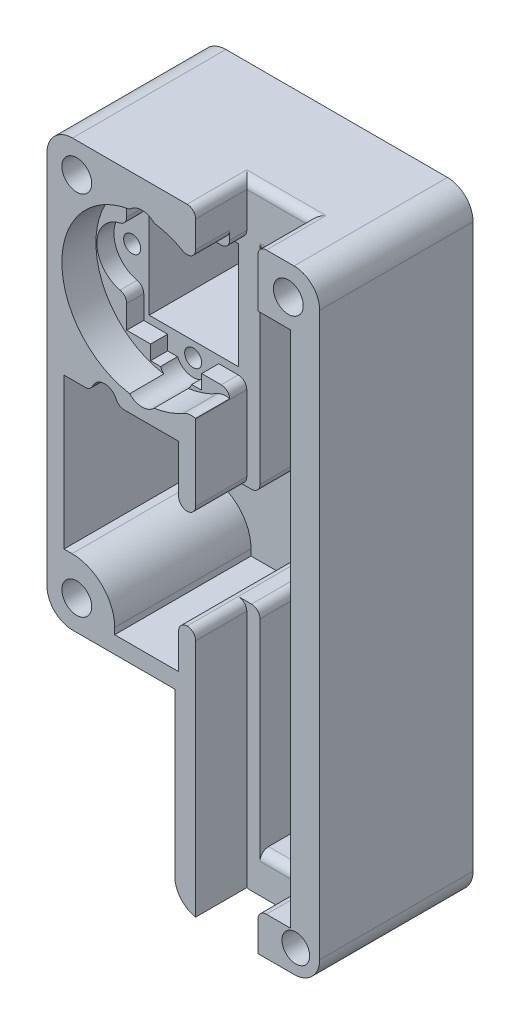
SolidWorks part; units mm, degrees
ref_plane "Ebene vorne" through (0, 0, 0) normal (0, 0, 1) x (1, 0, 0)
ref_plane "Ebene oben" through (0, 0, 0) normal (0, 1, 0) x (1, 0, 0)
ref_plane "Ebene rechts" through (0, 0, 0) normal (1, 0, 0) x (0, 0, -1)
sketch "body-sketch" plane through (0, 0, 0) normal (0, 0, 1) x (1, 0, 0)
  line L0 (-32, 50) -> (0, 50)
  line L1 (-32, 0) -> (-17, 0)
  line L2 (0, 50) -> (0, -22)
  line L3 (-17, -22) -> (-17, 0)
  line L4 (-32, 0) -> (-32, 50)
  line L5 (0, -22) -> (-17, -22)
  line L7 (-26, 43) -> (-15.5, 43)
  line L8 (-26, 43) -> (-26, 30.5)
  line L9 (-26, 30.5) -> (-15.5, 30.5)
  line L10 (-15.5, 43) -> (-15.5, 30.5)
  dimension "D1" = 32
  dimension "D2" = 50
  dimension "D3" = 17
  dimension "D4" = 72
  dimension "D5" = 12.5
  dimension "D6" = 10.5
  dimension "D7" = 7
  dimension "D8" = 6
extrude "body" add sketch "body-sketch" along normal mid plane 18
sketch "gear_box" plane through (0, 0, 9) normal (0, 0, 1) x (1, 0, 0)
  line L0 (-26, 43) -> (-15.5, 30.5) construction
  line L1 (-15.5, 30.5) -> (-15.5, 43) construction
  line L2 (-15.5, 43) -> (-26, 30.5) construction
  line L3 (0, 50) -> (-32, 50) construction
  line L4 (-32, 50) -> (-32, 0) construction
  circle A0 centre (-20.75, 36.75) radius 9.5
  dimension "D1" = 19
  dimension "D2" = 13.25
  dimension "D3" = 11.25
extrude "gear_profile" cut sketch "gear_box" against normal blind 4
sketch "screwhole1" plane through (0, 0, 9) normal (0, 0, 1) x (1, 0, 0)
  line L0 (0, 50) -> (-32, 50) construction
  line L1 (-32, 50) -> (-32, 0) construction
  line L2 (0, -22) -> (0, 50) construction
  line L3 (-17, -22) -> (0, -22) construction
  circle A0 centre (-28.5, 46.5) radius 1.75
  circle A1 centre (-3.6772, 46.5) radius 1.75
  circle A2 centre (-2.8, -19.2) radius 1.625
  dimension "D1" = 3.5
  dimension "D4" = 3.25
  dimension "D2" = 3.5
  dimension "D3" = 3.5
  dimension "D5" = 2.8
  dimension "D6" = 2.8
extrude "screw1" cut sketch "screwhole1" against normal through all
fillet "Verrundung2" radius 3 2 edges at (0, 50, 0) (-32, 50, 0)
sketch "glider" plane through (0, 0, 9) normal (0, 0, 1) x (1, 0, 0)
  line L0 (-17, 0) -> (-17, -22) construction
  line L1 (-13, 43.3) -> (-3.4, 43.3)
  line L2 (-13, 43.3) -> (-13, -17.5)
  line L3 (-13, -17.5) -> (-3.4, -17.5)
  line L4 (-3.4, 43.3) -> (-3.4, -17.5)
  line L6 (-15.5, 43) -> (-26, 43) construction
  dimension "D1" = 9.6
  dimension "D2" = 60.8
  dimension "D3" = 4
  dimension "D4" = 3.4
  dimension "D5" = 0.3
extrude "glider_rut" cut sketch "glider" against normal blind 16
fillet "Verrundung4" radius 2 1 edges at (-13, 31.2557, 7)
sketch "holder of glider" plane through (0, 0, -7) normal (0, 0, 1) x (1, 0, 0)
  line L0 (-8.2, 43.3) -> (-8.2, -17.5) construction
  line L2 (-3.4, 43.3) -> (-13, 43.3) construction
  line L3 (-13, -17.5) -> (-3.4, -17.5) construction
  line L5 (-11.2, 30.8) -> (-5.2, 30.8)
  line L6 (-11.2, 30.8) -> (-11.2, 22.8)
  line L7 (-11.2, 22.8) -> (-5.2, 22.8)
  line L8 (-5.2, 30.8) -> (-5.2, 22.8)
  line L9 (-11.2, 3) -> (-5.2, 3)
  line L10 (-11.2, 3) -> (-11.2, -5)
  line L11 (-11.2, -5) -> (-5.2, -5)
  line L12 (-5.2, 3) -> (-5.2, -5)
  line L13 (-11.2, 3) -> (-5.2, -5) construction
  line L14 (-11.2, -5) -> (-5.2, 3) construction
  line L15 (-11.2, 30.8) -> (-5.2, 22.8) construction
  line L16 (-11.2, 22.8) -> (-5.2, 30.8) construction
  point P6 (-8.2, 26.8)
  point P9 (-8.2, -1)
  dimension "D1" = 16.5
  dimension "D2" = 6
  dimension "D3" = 8
  dimension "D4" = 16.5
  dimension "D5" = 8
  dimension "D6" = 6
extrude "glider-holder" add sketch "holder of glider" along normal blind 4.3
fillet "Verrundung5" radius 2 8 edges at (-11.2, -5, -4.85) (-5.2, -5, -4.85) (-5.2, 3, -4.85) (-11.2, 3, -4.85) (-11.2, 30.8, -4.85) (-5.2, 30.8, -4.85) (-5.2, 22.8, -4.85) (-11.2, 22.8, -4.85)
fillet "Verrundung6" radius 1 8 edges at (-5.2, 26.8, -7) (-5.7858, 30.2142, -7) (-8.2, 30.8, -7) (-10.6142, 30.2142, -7) (-11.2, 26.8, -7) (-10.6142, 23.3858, -7) (-8.2, 22.8, -7) (-5.7858, 23.3858, -7)
fillet "Verrundung7" radius 1 8 edges at (-5.2, -1, -7) (-5.7858, 2.4142, -7) (-8.2, 3, -7) (-10.6142, 2.4142, -7) (-11.2, -1, -7) (-10.6142, -4.4142, -7) (-8.2, -5, -7) (-5.7858, -4.4142, -7)
sketch "Pinion rut" plane through (0, 0, 9) normal (0, 0, 1) x (1, 0, 0)
  line L0 (-9.5, 50) -> (-9.5, -22) construction
  line L1 (-3, 50) -> (-29, 50) construction
  line L2 (-17, -22) -> (0, -22) construction
  line L3 (0, -22) -> (0, 47) construction
  line L4 (-9.5, 14) -> (0, 14) construction
  line L6 (-11.75, 50) -> (-7.25, 50)
  line L7 (-11.75, 50) -> (-11.75, -22)
  line L8 (-11.75, -22) -> (-7.25, -22)
  line L9 (-7.25, 50) -> (-7.25, -22)
  line L10 (-11.75, 50) -> (-7.25, -22) construction
  line L11 (-11.75, -22) -> (-7.25, 50) construction
  dimension "D1" = 9.5
  dimension "D2" = 4.5
extrude "pinion rut cut" cut sketch "Pinion rut" against normal blind 5
fillet "Verrundung8" radius 2 1 edges at (-13, 42.2443, 7)
sketch "sketch pinion channel" plane through (0, 0, 9) normal (0, 0, 1) x (1, 0, 0)
  line L1 (-7.25, 50) -> (-14.55, 50)
  line L2 (-7.25, 50) -> (-7.25, -25)
  line L3 (-7.25, -25) -> (-14.55, -25)
  line L4 (-14.55, 50) -> (-14.55, -25)
  dimension "D1" = 7.3
  dimension "D2" = 75
extrude "pinion channel" cut sketch "sketch pinion channel" against normal blind 6
fillet "Verrundung9" radius 1 1 edges at (-14.55, 43.9479, 7)
fillet "Verrundung10" radius 1 3 edges at (-7.25, -17.5, 6) (-7.25, 50, 6) (-14.55, 50, 6)
fillet "Verrundung11" radius 1 3 edges at (-10.125, 43.3, 3) (-9.625, -17.5, 3) (-10.9, 50, 3)
sketch "motor-holder" plane through (0, 0, 5) normal (0, 0, 1) x (1, 0, 0)
  line L0 (-14.3394, 43.85) -> (-14.3394, 29.65)
  line L1 (-15.5, 30.5) -> (-15.5, 43) construction
  line L2 (-15.5, 30.5) -> (-15.5, 43) construction
  line L3 (-15.5, 43) -> (-26, 43) construction
  line L4 (-17.8394, 27.95) -> (-17.8394, 29.65)
  line L7 (-20.75, 46.25) -> (-20.75, 27.25) construction
  line L8 (-26, 44.6675) -> (-26, 28.8325) construction
  line L9 (-26.6394, 43.85) -> (-23.8394, 43.85)
  line L10 (-23.8394, 45.55) -> (-17.8394, 45.55)
  line L11 (-23.8394, 43.85) -> (-23.8394, 45.55)
  line L12 (-23.8394, 27.95) -> (-17.8394, 27.95)
  line L13 (-17.8394, 29.65) -> (-14.3394, 29.65)
  line L14 (-17.8394, 45.55) -> (-17.8394, 43.85)
  line L15 (-17.8394, 43.85) -> (-14.3394, 43.85)
  line L17 (-26.6394, 43.85) -> (-26.6394, 29.65)
  line L23 (-23.8394, 27.95) -> (-23.8394, 29.65)
  line L24 (-23.8394, 29.65) -> (-26.6394, 29.65)
  arc A0 (-16.0452, 45.0032) -> (-16, 28.5228) centre (-20.75, 36.75) ccw construction
  arc A1 (-16.0452, 45.0032) -> (-16, 28.5228) centre (-20.75, 36.75) ccw construction
  point P25 (-20.75, 36.75)
  point P30 (-20.75, 36.75)
  dimension "D1" = 17.6
  dimension "D2" = 6
  dimension "D3" = 14.2
  dimension "D4" = 3.5
  dimension "D5" = 2.8
extrude "motor -holder" cut sketch "motor-holder" against normal blind 2
sketch "Skizze1" plane through (0, 0, 3) normal (0, 0, 1) x (1, 0, 0)
  line L0 (-20.8394, 45.55) -> (-20.8394, 27.95) construction
  line L1 (-17.8394, 45.55) -> (-23.8394, 45.55) construction
  line L2 (-23.8394, 27.95) -> (-17.8394, 27.95) construction
  line L3 (-26, 36.75) -> (-15.5, 36.75) construction
  line L4 (-26, 30.5) -> (-26, 43) construction
  line L5 (-15.5, 43) -> (-15.5, 30.5) construction
  circle A0 centre (-20.8394, 28.75) radius 1
  circle A1 centre (-20.8394, 44.75) radius 1
  point P16 (-20.8394, 36.75)
  dimension "D1" = 2
  dimension "D2" = 16
  dimension "D3" = 8
extrude "motor-screw" cut sketch "Skizze1" against normal blind 10
sketch "Skizze2" plane through (0, 0, 5) normal (0, 0, 1) x (1, 0, 0)
  circle A0 centre (-20.8394, 44.75) radius 2
  circle A1 centre (-20.8394, 28.75) radius 2
  dimension "D1" = 4
extrude "Schnitt-Linear austragen2" cut sketch "Skizze2" against normal blind 2 and the other way through all
sketch "Skizze3" plane through (0, 0, 5) normal (0, 0, 1) x (1, 0, 0)
  line L0 (-30.25, 36.75) -> (-13, 36.75) construction
  line L1 (-13, 44.3) -> (-13, -18.5) construction
  line L2 (-26.6394, 43.85) -> (-26.6394, 29.65) construction
  line L3 (-26.6394, 43.85) -> (-26.6394, 29.65) construction
  line L4 (-26.6394, 40.25) -> (-26.6394, 33.25)
  line L5 (-26.6394, 33.25) -> (-26.6589, 33.311)
  arc A0 (-22.2928, 46.1239) -> (-22.2928, 27.3761) centre (-20.75, 36.75) ccw construction
  arc A1 (-26.6394, 40.25) -> (-26.6394, 33.25) centre (-26.6394, 36.75) ccw
  point P8 (-26.6394, 36.75)
  line M6 (-26.6394, 29.65) -> (-26.6394, 43.85)
  dimension "D1" = 3.5
extrude "Schnitt-Linear austragen3" cut sketch "Skizze3" against normal blind 2 contours A1 L0 L4 | L0 A1 M6 region at (-28.1249, 38.2354, 5) region at (-28.1249, 35.2646, 5)
fillet "Verrundung12" radius 1 2 edges at (-14.55, 29.65, 4) (-14.55, 43.85, 4)
fillet "Verrundung13" radius 1 2 edges at (-26.6394, 33.25, 4) (-26.6394, 40.25, 4)
sketch "left hole" plane through (0, 0, 3) normal (0, 0, 1) x (1, 0, 0)
  line L0 (-30.1394, 36.75) -> (-15.5, 36.75) construction
  line L1 (-15.5, 43) -> (-15.5, 30.5) construction
  line L2 (-20.75, 43) -> (-20.75, 30.5) construction
  line L3 (-26, 43) -> (-15.5, 43) construction
  line L4 (-15.5, 30.5) -> (-26, 30.5) construction
  arc A0 (-27.4172, 40.1625) -> (-27.4172, 33.3375) centre (-26.6394, 36.75) ccw construction
  circle A1 centre (-28, 36.75) radius 1
  point P15 (-20.75, 36.75)
  dimension "D1" = 2
  dimension "D2" = 7.25
extrude "center-hole-left" cut sketch "left hole" against normal blind 10
sketch "cage" plane through (0, 0, 9) normal (0, 0, 1) x (1, 0, 0)
  line L2 (-30, 25.4121) -> (-30, 7.738)
  line L3 (-30, 25.4121) -> (-16.55, 25.4121)
  line L4 (-16.55, 25.4121) -> (-16.55, 18.8066)
  line L5 (-16.55, 18.8066) -> (-7.442, 18.8066)
  line L6 (-7.442, 18.8066) -> (-7.442, 7.14)
  line L7 (-14.55, 28.65) -> (-14.55, -22) construction
  line L8 (-14.55, 28.65) -> (-14.55, -22) construction
  line L9 (-7.442, 7.14) -> (-16.55, 7.14)
  line L10 (-16.55, 7.14) -> (-16.55, 2)
  line L11 (-30, 7.738) -> (-24.0525, 7.738)
  line L13 (-24.0525, 7.738) -> (-24.0525, 2)
  line L14 (-24.0525, 2) -> (-16.55, 2)
  point P7 (-24.0525, 13.9213)
  dimension "D2" = 2
  dimension "D3" = 2
extrude "electro-cage" cut sketch "cage" against normal blind 16
sketch "Skizze6" plane through (0, 0, 9) normal (0, 0, 1) x (1, 0, 0)
  line L0 (-16.55, 25.4121) -> (-30, 25.4121) construction
  circle A0 centre (-25.2373, 25.4121) radius 1.5
  dimension "D1" = 3
extrude "Schnitt-Linear austragen5" cut sketch "Skizze6" against normal blind 18
sketch "Skizze7" plane through (0, 0, 9) normal (0, 0, 1) x (1, 0, 0)
  line L0 (-32, 0) -> (-17, 0) construction
  line L1 (-32, 47) -> (-32, 0) construction
  circle A0 centre (-28.5, 3.5) radius 1.75
  dimension "D1" = 3.5
  dimension "D3" = 3.5
  dimension "D2" = 3.5
extrude "Schnitt-Linear austragen6" cut sketch "Skizze7" against normal blind 18
fillet "Verrundung14" radius 3 1 edges at (-32, 0, 0)
fillet "Verrundung15" radius 5 1 edges at (-24.0525, 7.738, 1)
fillet "Verrundung16" radius 1 1 edges at (-16.55, 18.8066, 1)
fillet "Verrundung17" radius 1 1 edges at (-16.55, 7.14, 1)
fillet "Verrundung18" radius 1 1 edges at (-23.7373, 25.4121, 1)
fillet "Verrundung19" radius 1 4 edges at (-13, 18.8066, -2) (-13, 7.14, -2) (-14.55, 7.14, 6) (-14.55, 18.8066, 6)
fillet "Verrundung20" radius 1 1 edges at (-26.7373, 25.4121, 1)
fillet "Verrundung21" radius 3 2 edges at (-17, -22, 0) (0, -22, 0)
